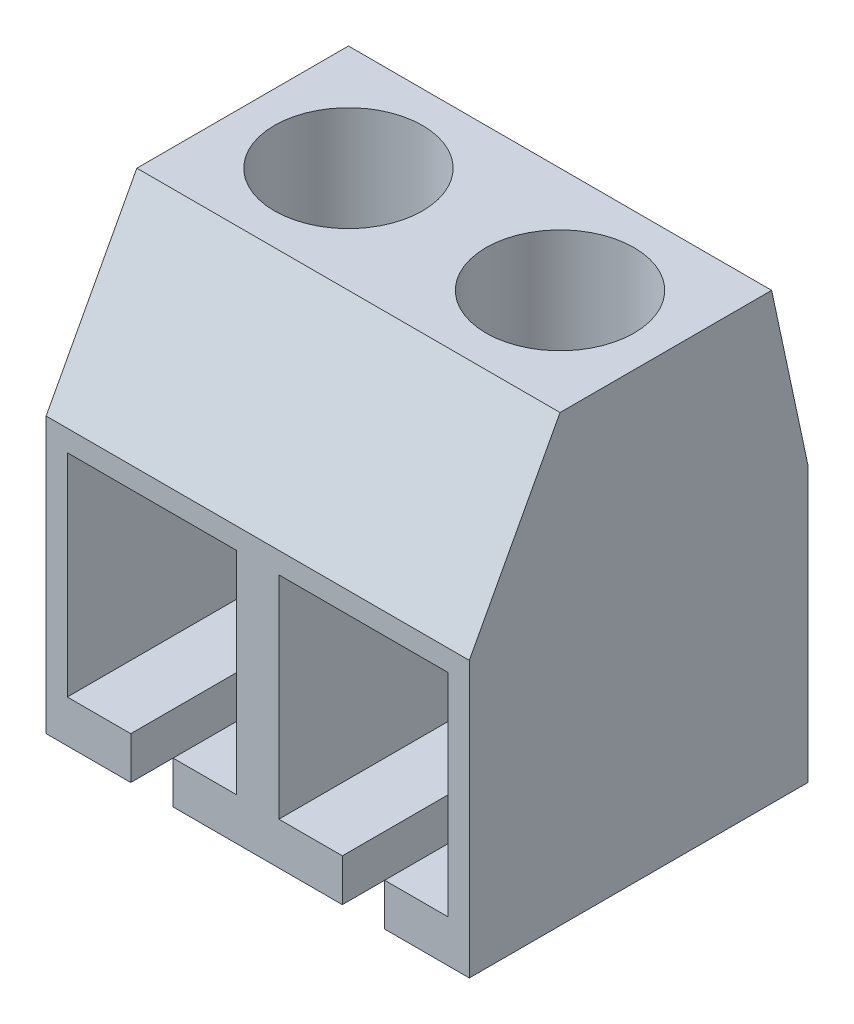
SolidWorks part; units mm, degrees
ref_plane "Ön Düzlem" through (0, 0, 0) normal (0, 0, 1) x (1, 0, 0)
ref_plane "Üst Düzlem" through (0, 0, 0) normal (0, 1, 0) x (1, 0, 0)
ref_plane "Sağ Düzlem" through (0, 0, 0) normal (1, 0, 0) x (0, 0, -1)
sketch "Çizim1" plane through (0, 0, 0) normal (1, 0, 0) x (0, 0, -1)
  line L0 (-4, 1) -> (4, 1) construction
  line L1 (-1.8562, 5) -> (3.1438, 5)
  line L2 (-4, 1) -> (-4, -5.5)
  line L3 (-4, -5.5) -> (4, -5.5)
  line L4 (4, 1) -> (4, -5.5)
  line L5 (-2.6115, 3.5908) -> (4, -5.5) construction
  line L6 (-4, -5.5) -> (3.2558, 4.4767) construction
  line L7 (-4, 1) -> (-1.8562, 5)
  line L8 (4, 1) -> (3.1438, 5)
  point P0 (0, 0)
  dimension "D1" = 10.5
  dimension "D2" = 8
  dimension "D3" = 4
  dimension "D4" = 5
extrude "Yükseklik-Ekstrüzyon1" add sketch "Çizim1" along normal blind 5 and the other way blind 5
sketch "Çizim2" plane through (0, 0, -4) normal (0, 0, -1) x (-1, 0, 0)
  line L0 (0, 1) -> (0, -5.5) construction
  line L1 (5, 1) -> (-5, 1) construction
  line L2 (5, -5.5) -> (-5, -5.5) construction
  line L3 (-4.5, 1) -> (-4.5, -5.5) construction
  line L4 (-5, -5.5) -> (-5, 1) construction
  line L5 (-2.5, 1) -> (-2.5, -5.5) construction
  line L6 (-5, 0.5) -> (5, 0.5) construction
  line L7 (5, -5.5) -> (5, 1) construction
  line L8 (-5, -4.5) -> (-3, -4.5) construction
  line L9 (-3, -4.5) -> (-3, -5.5)
  line L10 (-4.5, 0.5) -> (-0.5, 0.5)
  line L11 (-4.5, 0.5) -> (-4.5, -4.5)
  line L12 (-4.5, -4.5) -> (-3, -4.5)
  line L13 (-0.5, 0.5) -> (-0.5, -4.5)
  line L14 (-2, -4.5) -> (-2, -5.5)
  line L15 (-3, -5.5) -> (-2, -5.5)
  line L16 (-2, -4.5) -> (5, -4.5) construction
  line L17 (-2, -4.5) -> (-0.5, -4.5)
  line L18 (2, -4.5) -> (2, -5.5)
  line L19 (3, -5.5) -> (2, -5.5)
  line L20 (3, -4.5) -> (3, -5.5)
  line L21 (4.5, -4.5) -> (3, -4.5)
  line L22 (4.5, 0.5) -> (4.5, -4.5)
  line L23 (4.5, 0.5) -> (0.5, 0.5)
  line L24 (0.5, 0.5) -> (0.5, -4.5)
  line L25 (2, -4.5) -> (0.5, -4.5)
  point P24 (-3, -5)
  dimension "D1" = 0.5
  dimension "D2" = 2.5
  dimension "D3" = 6
  dimension "D4" = 1
  dimension "D5" = 4
  dimension "D6" = 0.5
extrude "Kes-Ekstrüzyon1" cut sketch "Çizim2" against normal blind 10
sketch "Çizim3" plane through (0, 5, 0) normal (0, 1, 0) x (1, 0, 0)
  line L0 (-5, 0.6438) -> (5, 0.6438) construction
  line L1 (-5, 3.1438) -> (-5, -1.8562) construction
  line L2 (5, 3.1438) -> (5, -1.8562) construction
  circle A0 centre (-2.5, 0.6438) radius 1.75
  circle A1 centre (2.5, 0.6438) radius 1.75
  dimension "D1" = 3.5
  dimension "D3" = 3.5
  dimension "D4" = 2.5
  dimension "D2" = 2.5
extrude "Kes-Ekstrüzyon2" cut sketch "Çizim3" against normal blind 7
